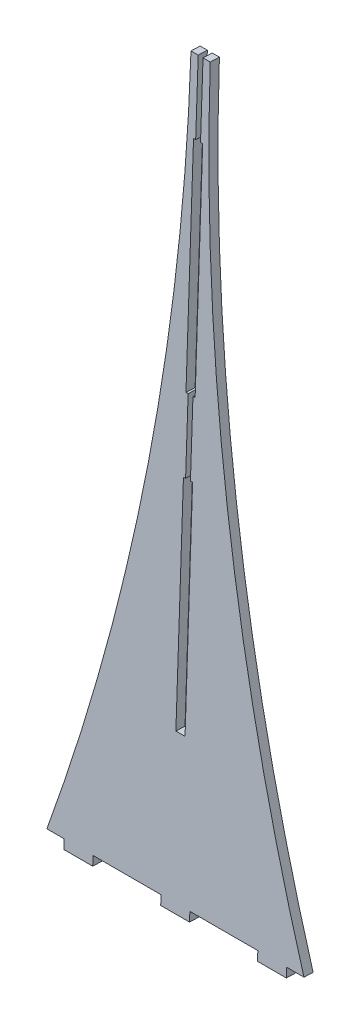
SolidWorks part; units mm, degrees
ref_plane "Front Plane" through (0, 0, 0) normal (0, 0, 1) x (1, 0, 0)
ref_plane "Top Plane" through (0, 0, 0) normal (0, 1, 0) x (1, 0, 0)
ref_plane "Right Plane" through (0, 0, 0) normal (1, 0, 0) x (0, 0, -1)
sketch "Sketch1" plane through (0, -2.4223, -69.3084) normal (0, -0.0349, -0.9994) x (-1, 0, 0)
  line L0 (0, 6.6089) -> (0, -6.6089) construction
  line L1 (3.3375, 329.2146) -> (0.8375, 329.2146)
  line L2 (-44.5715, 79.2146) -> (44.5715, 79.2146)
  line L3 (0.8375, 329.2146) -> (0.8375, 304.2146)
  line L4 (-0.8375, 304.2146) -> (-1.5875, 304.2146)
  line L5 (-3.3375, 329.2146) -> (-0.8375, 329.2146)
  line L6 (-0.8375, 329.2146) -> (-0.8375, 304.2146)
  line L7 (-1.5875, 304.2146) -> (-1.5875, 329.2146) construction
  line L8 (-1.5875, 304.2146) -> (-1.5875, 229.2146)
  line L9 (-1.5875, 229.2146) -> (-0.8375, 229.2146)
  line L10 (-0.8375, 229.2146) -> (-0.8375, 204.2146)
  line L11 (-1.5875, 204.2146) -> (1.5875, 204.2146) construction
  line L12 (-0.8375, 204.2146) -> (-1.5875, 204.2146)
  line L13 (-1.5875, 204.2146) -> (-1.5875, 129.2146)
  line L14 (-1.5875, 129.2146) -> (1.5875, 129.2146)
  line L15 (-1.5875, 129.2146) -> (1.5875, 129.2146) construction
  line L16 (1.5875, 79.2146) -> (1.5875, 129.2146) construction
  line L17 (-1.5875, 229.2146) -> (1.5875, 229.2146) construction
  line L19 (-38.5715, 79.2146) -> (-38.5715, 76.0396)
  line L20 (-38.5715, 76.0396) -> (-28.5715, 76.0396)
  line L21 (-28.5715, 76.0396) -> (-28.5715, 79.2146)
  line L22 (0.8375, 304.2146) -> (1.5875, 304.2146)
  line L23 (1.5875, 304.2146) -> (1.5875, 229.2146)
  line L24 (1.5875, 229.2146) -> (0.8375, 229.2146)
  line L25 (0.8375, 229.2146) -> (0.8375, 204.2146)
  line L26 (0.8375, 204.2146) -> (1.5875, 204.2146)
  line L27 (1.5875, 204.2146) -> (1.5875, 129.2146)
  line L28 (28.5715, 76.0396) -> (28.5715, 79.2146)
  line L29 (38.5715, 76.0396) -> (28.5715, 76.0396)
  line L30 (38.5715, 79.2146) -> (38.5715, 76.0396)
  line L31 (-5, 79.2146) -> (-5, 76.0396)
  line L32 (-5, 76.0396) -> (5, 76.0396)
  line L33 (5, 76.0396) -> (5, 79.2146)
  arc A0 (-44.5715, 79.2146) -> (-3.3375, 329.2146) centre (-781.825, 329.2146) ccw
  arc A1 (44.5715, 79.2146) -> (3.3375, 329.2146) centre (781.825, 329.2146) cw
  point P2 (-44.5715, 79.2146)
  point P53 (0, 76.0396)
  point P56 (0, 79.2146)
  line M3 (1.5875, 79.2146) -> (1.5875, 129.2146)
  line M4 (1.5875, 129.2146) -> (-1.5875, 129.2146)
  line M5 (-1.5875, 129.2146) -> (-1.5875, 79.2146)
  line M6 (-1.5875, 79.2146) -> (1.5875, 79.2146)
  dimension "D1" = 0.75
  dimension "D2" = 2.5
  dimension "D3" = 3.175
  dimension "D4" = 10
  dimension "D5" = 6
extrude "Boss-Extrude1" add sketch "Sketch1" along normal blind 3.175 contours A0 L2 L13 L12 L10 L9 L8 L4 L6 L5 M5 | L2 A1 L1 L3 L22 L23 L24 L25 L26 L27 M3 | L32 L33 L2 L31 M6 | L30 L2 L28 L29 | M6 M3 M4 M5 | L20 L21 L2 L19 region at (-14.0204, 147.1748, -74.5368) region at (-33.5715, 75.1575, -72.0198) region at (0, 75.1575, -72.0198) region at (0, 101.7287, -72.9484) region at (14.0204, 147.1748, -74.5368) region at (33.5715, 75.1575, -72.0198)
